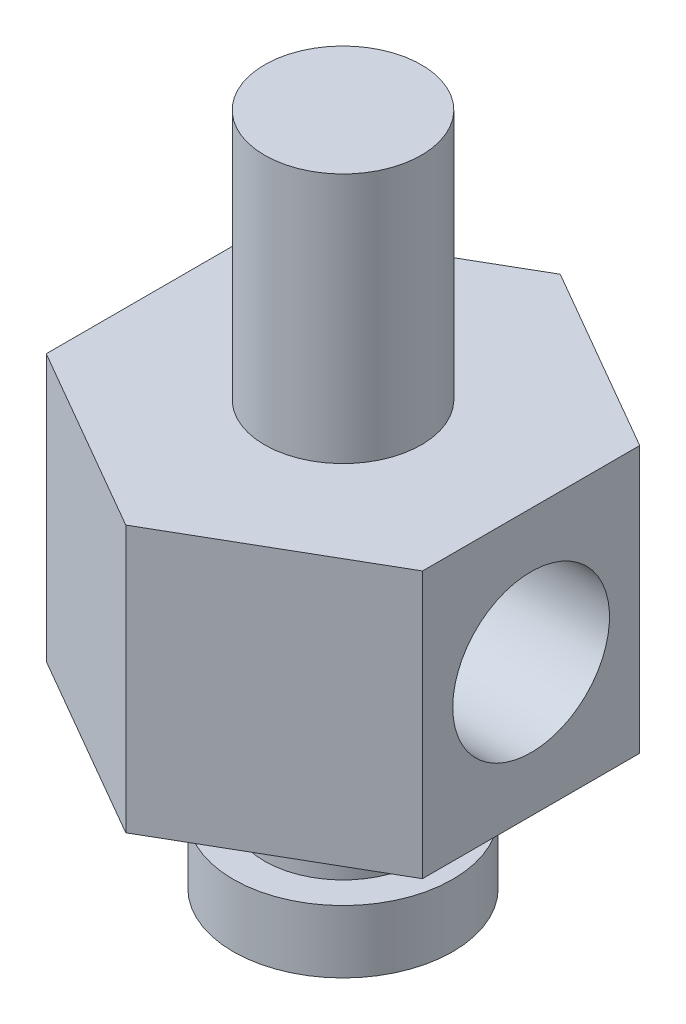
SolidWorks part; units mm, degrees
ref_plane "Plan de face" through (0, 0, 0) normal (0, 0, 1) x (1, 0, 0)
ref_plane "Plan de dessus" through (0, 0, 0) normal (0, 1, 0) x (1, 0, 0)
ref_plane "Plan de droite" through (0, 0, 0) normal (1, 0, 0) x (0, 0, -1)
sketch "Esquisse1" plane through (0, 0, 0) normal (0, 1, 0) x (1, 0, 0)
  circle A0 centre (0, 0) radius 1.5
  circle A1 centre (0, 0) radius 3.5
  dimension "D1" = 7
  dimension "D2" = 3
extrude "Boss.-Extru.1" add sketch "Esquisse1" along normal blind 2
sketch "Esquisse2" plane through (0, 2, 0) normal (0, 1, 0) x (1, 0, 0)
  circle A0 centre (0, 0) radius 1.5
  circle A1 centre (0, 0) radius 2.5
  dimension "D1" = 3
  dimension "D2" = 5
extrude "Boss.-Extru.2" add sketch "Esquisse2" along normal blind 3
sketch "Esquisse3" plane through (0, 5, 0) normal (0, 1, 0) x (1, 0, 0)
  line L0 (-6, 3.4641) -> (-6, -3.4641)
  line L1 (-6, -3.4641) -> (0, -6.9282)
  line L2 (0, -6.9282) -> (6, -3.4641)
  line L3 (6, -3.4641) -> (6, 3.4641)
  line L4 (6, 3.4641) -> (0, 6.9282)
  line L5 (0, 6.9282) -> (-6, 3.4641)
  line L6 (-6, 3.4641) -> (6, 3.4641) construction
  line L7 (-6, 3.4641) -> (6, -3.4641) construction
  circle A0 centre (0, 0) radius 1.5
  point P6 (0, 0)
  dimension "D3" = 3
  dimension "D1" = 12
  dimension "D2" = 12
extrude "Boss.-Extru.3" add sketch "Esquisse3" along normal blind 8.5
sketch "Esquisse4" plane through (0, 13.5, 0) normal (0, 1, 0) x (1, 0, 0)
  circle A0 centre (0, 0) radius 2.5
  dimension "D1" = 5
extrude "Boss.-Extru.4" add sketch "Esquisse4" along normal blind 8
sketch "Esquisse5" plane through (-6, 0, 0) normal (-1, 0, 0) x (0, 0, 1)
  line L0 (-3.4641, 13.5) -> (3.4641, 5) construction
  circle A0 centre (0, 9.25) radius 2.5
  dimension "D1" = 5
extrude "Enlèv. mat.-Extru.1" cut sketch "Esquisse5" against normal up to surface (12 mm away) up to face at (6, 9.25, 0)
